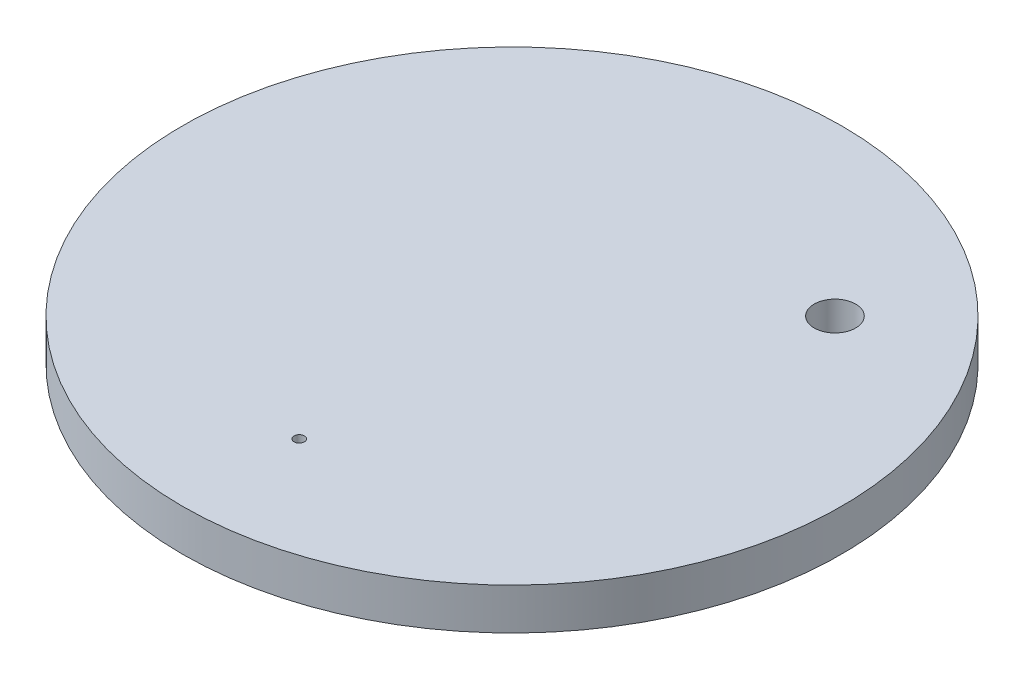
SolidWorks part; units mm, degrees
material "1060 Alloy"
ref_plane "Front Plane" through (0, 0, 0) normal (0, 0, 1) x (1, 0, 0)
ref_plane "Top Plane" through (0, 0, 0) normal (0, 1, 0) x (1, 0, 0)
ref_plane "Right Plane" through (0, 0, 0) normal (1, 0, 0) x (0, 0, -1)
sketch "Sketch1" plane through (0, 0, 0) normal (0, 1, 0) x (1, 0, 0)
  circle A0 centre (0, 0) radius 15.875
  dimension "D1" = 31.75
extrude "Boss-Extrude1" add sketch "Sketch1" along normal blind 1
sketch "Sketch5" plane through (0, 0, 0) normal (0, -1, 0) x (1, 0, 0)
  circle A0 centre (0, 0) radius 6.9
  dimension "D1" = 13.8
extrude "Boss-Extrude2" add sketch "Sketch5" along normal blind 0.5
sketch "Sketch6" plane through (0, 0, 0) normal (0, -1, 0) x (1, 0, 0)
  circle A0 centre (0, 0) radius 15.875
  circle A1 centre (0, 0) radius 9.525
  circle A2 centre (0, 0) radius 15.875 construction
  dimension "D1" = 0
  dimension "D2" = 19.05
extrude "Boss-Extrude3" add sketch "Sketch6" along normal blind 1
thread "Thread1" pitch 0.25 method cut profile "Thread Profile1" start angle 0, offset 0, length 1, pitch 0.25, diameter 19.05
ref_plane "Plane1" through (9.525, -1, 0) normal (0, 0, 1) x (1, 0, 0)
sketch "Thread Profile1" plane through (9.525, -1, 0) normal (0, 0, 1) x (1, 0, 0)
  line L0 (0, 0) -> (0, 0.25) construction
  line L1 (0, 0) -> (0.1353, 0.0781)
  line L2 (0.1353, 0.0781) -> (0.1353, 0.1094)
  line L3 (0.1353, 0.1094) -> (0, 0.1875)
  line L4 (0.1353, 0.0937) -> (0, 0.0937) construction
  line L11 (0, 0) -> (0, 0.1875)
  point P2 (0, 0)
  dimension "Pitch" = 0.25
  dimension "Profile_Angle" = 60
  dimension "Profile_Land" = 0.0312
  dimension "Profile_Height" = 0.1353
sketch "Sketch7" plane through (0, 1, 0) normal (0, 1, 0) x (1, 0, 0)
  circle A0 centre (0, -10.25) radius 0.25
  circle A1 centre (0, 0) radius 9.8
  dimension "D1" = 0.5
  dimension "D2" = 10.25
  dimension "D3" = 19.6
extrude "Cut-Extrude1" cut sketch "Sketch7" against normal through all both and the other way through all contours A1 A0 region at (0, 1, 10.25)
sketch "Sketch8" plane through (0, 1, 0) normal (0, 1, 0) x (1, 0, 0)
  line L0 (0, 0) -> (13.2071, 13.2071) construction
  circle A0 centre (7.7782, 7.7782) radius 1
  dimension "D1" = 2
  dimension "D2" = 11
extrude "Cut-Extrude2" cut sketch "Sketch8" against normal through all both and the other way through all
